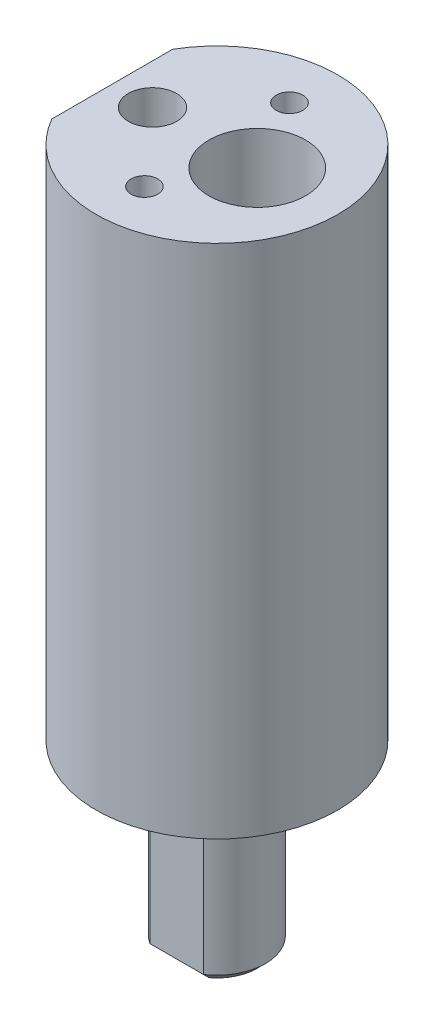
SolidWorks part; units mm, degrees
ref_plane "Front Plane" through (0, 0, 0) normal (0, 0, 1) x (1, 0, 0)
ref_plane "Top Plane" through (0, 0, 0) normal (0, 1, 0) x (1, 0, 0)
ref_plane "Right Plane" through (0, 0, 0) normal (1, 0, 0) x (0, 0, -1)
sketch "Sketch1" plane through (0, 0, 0) normal (0, 1, 0) x (1, 0, 0)
  line L0 (-3.3166, -5) -> (3.3166, -5)
  arc A0 (3.3166, -5) -> (-3.3166, -5) centre (0, 0) ccw
  dimension "D1" = 12
  dimension "D2" = 5
extrude "Boss-Extrude1" add sketch "Sketch1" along normal blind 22
sketch "Sketch2" plane through (0, 22, 0) normal (0, 1, 0) x (1, 0, 0)
  line L0 (-13, 7.4833) -> (-13, -7.4833)
  arc A0 (-13, -7.4833) -> (-13, 7.4833) centre (0, 0) ccw
  dimension "D1" = 30
  dimension "D2" = 13
extrude "Boss-Extrude2" add sketch "Sketch2" along normal blind 64
sketch "Sketch3" plane through (0, 86, 0) normal (0, 1, 0) x (1, 0, 0)
  line L0 (0, 0) -> (-14.4797, 0) construction
  circle A0 centre (-8, 0) radius 3
  dimension "D2" = 6
  dimension "D1" = 8
extrude "Cut-Extrude1" cut sketch "Sketch3" against normal blind 65
sketch "Sketch4" plane through (0, 86, 0) normal (0, 1, 0) x (1, 0, 0)
  circle A0 centre (5, 0) radius 6
  dimension "D2" = 12
  dimension "D1" = 5
extrude "Cut-Extrude2" cut sketch "Sketch4" against normal blind 52
sketch "Sketch5" plane through (0, 86, 0) normal (0, 1, 0) x (1, 0, 0)
  line L0 (0, 9) -> (0, -9) construction
  dimension "D1" = 9
  dimension "D2" = 9
hole_wizard "M4 Tapped Hole1" positions "Sketch6" profile "Sketch7" tap size "M4" standard "ISO"
sketch "Sketch6" plane through (0, 86, 0) normal (0, 1, 0) x (1, 0, 0)
  point P0 (0, 9)
  point P3 (0, -9)
sketch "Sketch7" plane through (0, 86, -9) normal (1, 0, 0) x (0, 0, 1)
  line L0 (0, 0) -> (0, 14.9914)
  line L1 (0, 14.9914) -> (1.65, 14)
  line L2 (1.65, 14) -> (1.65, 0)
  line L5 (1.65, 0) -> (0, 0)
  line L10 (0, 14.9914) -> (-1.65, 14) construction
  line L11 (0, -6.35) -> (0, 107.95) construction
  dimension "Tap Drill Dia." = 3.3
  dimension "Tap Drill Depth" = 14
  dimension "Drill Angle" = 118
sketch "Sketch8" plane through (-13, 0, 0) normal (-1, 0, 0) x (0, 0, 1)
  line L0 (0, 22) -> (0, 86) construction
  line L1 (-3, 22) -> (3, 22) construction
  line L2 (-7.4833, 86) -> (7.4833, 86) construction
  circle A0 centre (0, 54) radius 2.5
  circle A1 centre (0, 25) radius 1.5
  dimension "D1" = 5
  dimension "D2" = 3
  dimension "D3" = 32
  dimension "D4" = 61
extrude "Cut-Extrude3" cut sketch "Sketch8" against normal up to next
sketch "Sketch9" plane through (-13, 0, 0) normal (-1, 0, 0) x (0, 0, 1)
  line L0 (0, 86) -> (0, 22) construction
  line L1 (-7.4833, 86) -> (7.4833, 86) construction
  line L2 (-7.4833, 22) -> (7.4833, 22) construction
  circle A0 centre (0, 76) radius 1
  circle A1 centre (0, 34) radius 1
  dimension "D1" = 2
  dimension "D2" = 2
  dimension "D3" = 10
  dimension "D4" = 52
extrude "Cut-Extrude4" cut sketch "Sketch9" against normal blind 15
chamfer "Chamfer1" distance 1 angle 45 2 edges at (0, 0, 5) (0, 0, -6)
